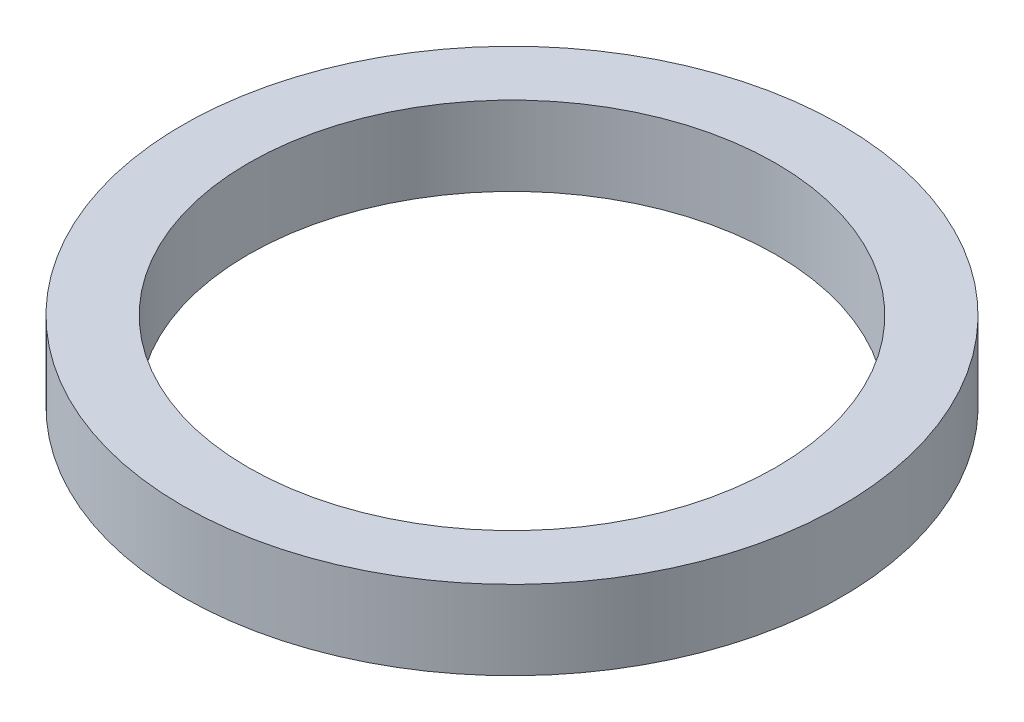
SolidWorks part; units mm, degrees
ref_plane "Front Plane" through (0, 0, 0) normal (0, 0, 1) x (1, 0, 0)
ref_plane "Top Plane" through (0, 0, 0) normal (0, 1, 0) x (1, 0, 0)
ref_plane "Right Plane" through (0, 0, 0) normal (1, 0, 0) x (0, 0, -1)
other "Bounding Box"
ref_plane "Default Plane" through (-8.9266, -12.7485, 0) normal (-0.1736, 0.9848, 0) x (0.9848, 0.1736, 0)
sketch "Sketch1" plane through (0, 0, 0) normal (0, 1, 0) x (1, 0, 0)
  circle A0 centre (0, 0) radius 20
  circle A1 centre (0, 0) radius 25
  dimension "D1" = 40
  dimension "D2" = 50
extrude "Boss-Extrude1" add sketch "Sketch1" along normal mid plane 6
